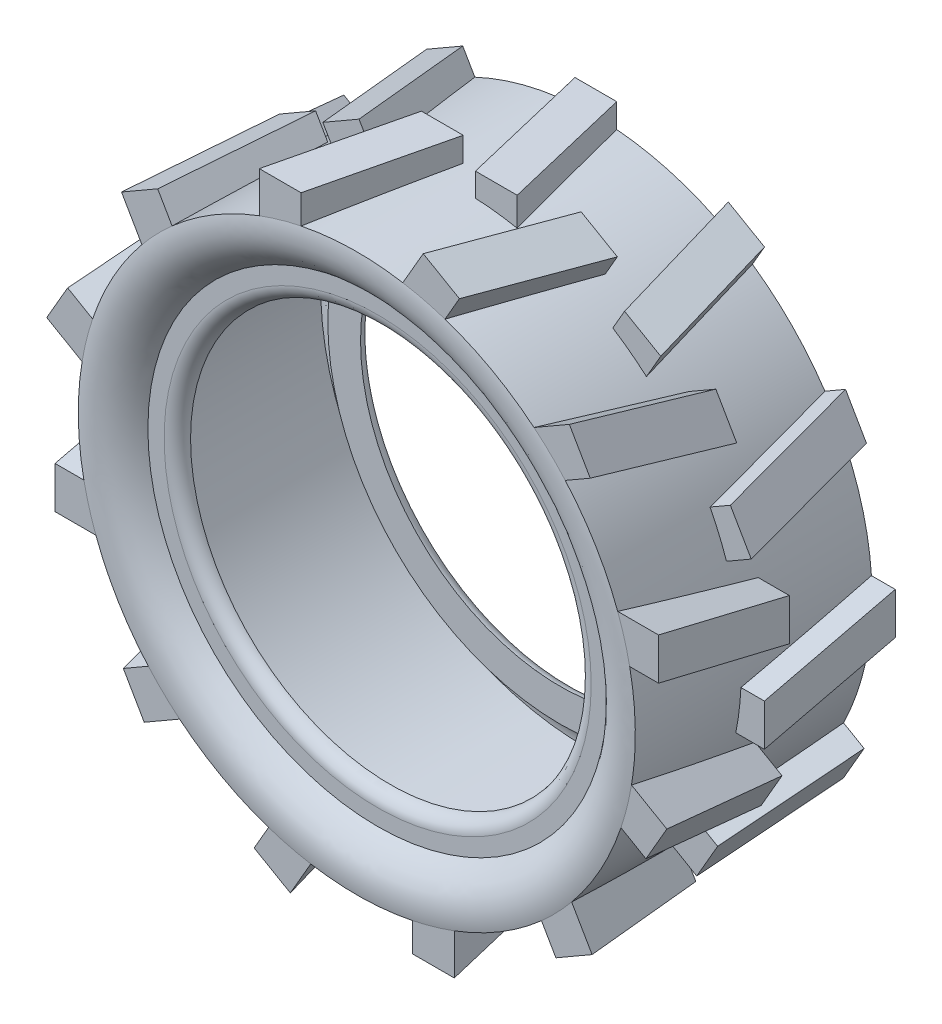
SolidWorks part; units mm, degrees
material "ABS"
ref_plane "Спереди" through (0, 0, 0) normal (0, 0, 1) x (1, 0, 0)
ref_plane "Сверху" through (0, 0, 0) normal (0, 1, 0) x (1, 0, 0)
ref_plane "Справа" through (0, 0, 0) normal (1, 0, 0) x (0, 0, -1)
sketch "Эскиз1" plane through (0, 0, 0) normal (1, 0, 0) x (0, 0, -1)
  line L0 (-131.0476, 0) -> (127.548, 0) construction
  line L1 (0, 0) -> (0, 104.7617) construction
  line L2 (0, 60) -> (25.5, 60)
  line L3 (21, 49.5) -> (21, 46)
  line L5 (18.3095, 50.0522) -> (18.3095, 46)
  line L14 (18.3095, 46) -> (18.3095, 43)
  line L16 (25.5, 60) -> (21, 49.5) construction
  line L17 (0, 57.3095) -> (21.4198, 57.3095) construction
  line L18 (21.4198, 57.3095) -> (18.3095, 50.0522) construction
  line L20 (19.831, 51.1228) -> (18.3095, 50.0522)
  line L21 (-19.831, 51.1228) -> (-18.3095, 50.0522)
  line L23 (-18.3095, 46) -> (-18.3095, 43)
  line L24 (-18.3095, 50.0522) -> (-18.3095, 46)
  line L25 (-21, 49.5) -> (-21, 46)
  line L26 (0, 60) -> (-25.5, 60)
  line L27 (0, 57) -> (23.7272, 57)
  line L28 (0, 57) -> (-23.7272, 57)
  line L32 (0, 58) -> (23.7544, 58) construction
  arc A0 (21, 46) -> (18.3095, 43) centre (18, 45.984) cw
  arc A1 (-21, 46) -> (-18.3095, 43) centre (-18, 45.984) ccw
  spline S0 degree 2 poles (25.5, 60) (26.8739, 53.7315) (21, 49.5) knots 0 0 0 1 1 1
  spline S1 degree 1 poles (23.7544, 58) (19.831, 51.1228) knots 0 0 1 1 construction
  spline S2 degree 3 poles (23.7544, 58) (23.7671, 57.6775) (23.7509, 57.0178) (23.5531, 55.812) (23.1145, 54.6722) (22.4028, 53.5614) (21.7154, 52.7344) (20.8801, 51.9263) (20.1802, 51.3744) (19.831, 51.1228) knots 0.157276 0.157276 0.157276 0.157276 0.262617 0.367957 0.578638 0.683979 0.789319 0.89466 1 1 1 1 only from (23.7272, 57) to (19.831, 51.1228)
  spline S3 degree 3 poles (-23.7272, 57) (-23.6981, 56.6959) (-23.5494, 55.8023) (-23.1145, 54.6722) (-22.4028, 53.5614) (-21.7154, 52.7344) (-20.8801, 51.9263) (-20.1802, 51.3744) (-19.831, 51.1228) knots 0.26618 0.26618 0.26618 0.26618 0.367957 0.578638 0.683979 0.789319 0.89466 1 1 1 1
  spline S4 degree 2 poles (-25.5, 60) (-26.8739, 53.7315) (-21, 49.5) knots 0 0 0 1 1 1
  point P32 (-23.7544, 57)
  dimension "D8" = 3
  dimension "D9" = 3
  dimension "D10" = 21
  dimension "D1" = 46
  dimension "D2" = 60
  dimension "D3" = 3.5
  dimension "D5" = 25.5
  dimension "D6" = 1.8603
  dimension "D7" = 4.0522
  dimension "D11" = 3
  dimension "D4" = 2
revolve "Повернуть1" add sketch "Эскиз1" angle 360 about L0
ref_plane "Плоскость1" through (0, 65, 0) normal (0, 1, 0) x (1, 0, 0)
sketch "Эскиз2" plane through (0, 65, 0) normal (0, 1, 0) x (1, 0, 0)
  line L0 (0, 31.0851) -> (0, -28.8708) construction
  line L1 (-48.8845, 0) -> (54.335, 0) construction
  line L2 (-5.2599, 2.6858) -> (-12, -25.5)
  line L3 (60, -25.5) -> (-60, -25.5) construction
  line L4 (-12, -25.5) -> (-21, -25.5)
  line L5 (-21, -25.5) -> (-14.2599, 2.6858)
  line L6 (-14.2599, 2.6858) -> (-5.2599, 2.6858)
  line L11 (5, 25.5) -> (-4, 25.5)
  line L12 (11.7401, -2.6858) -> (5, 25.5)
  line L13 (-4, 25.5) -> (2.7401, -2.6858)
  line L14 (2.7401, -2.6858) -> (11.7401, -2.6858)
  dimension "D1" = 9
  dimension "D2" = 21
  dimension "D3" = 5
extrude "Бобышка-Вытянуть1" add sketch "Эскиз2" against normal up to surface (6.7192 mm away) up to face at (60, 0, -25.5)
pattern_circular "Круговой массив1" count 12 over 360 about axis through (0, 0, 131.0476) along (0, 0, 1) of "Бобышка-Вытянуть1" reverse direction yes
